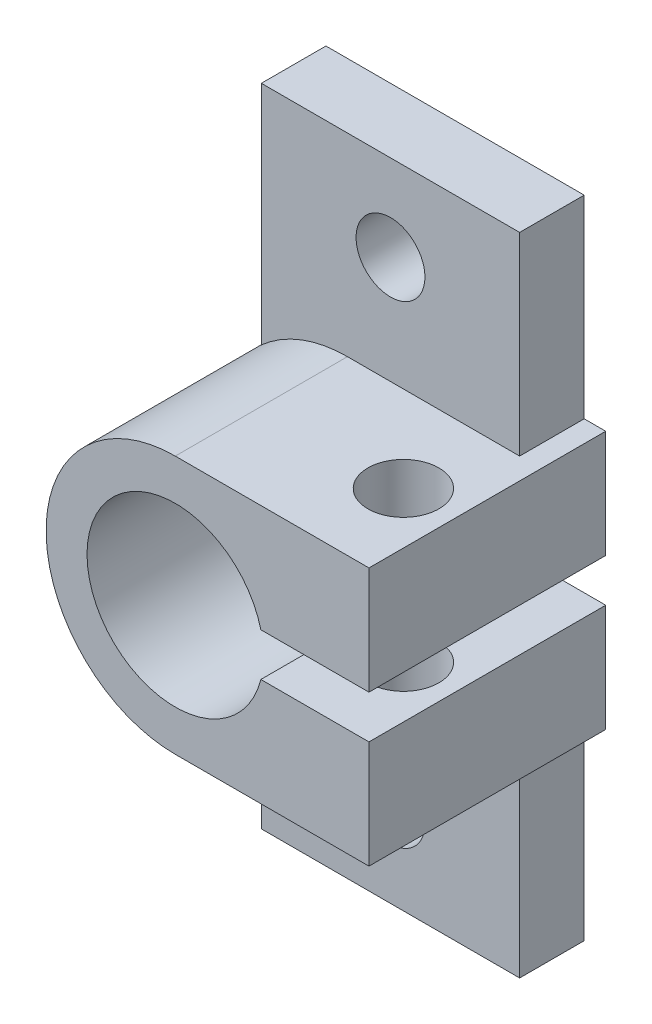
SolidWorks part; units mm, degrees
ref_plane "Plano frontal" through (0, 0, 0) normal (0, 0, 1) x (1, 0, 0)
ref_plane "Plano superior" through (0, 0, 0) normal (0, 1, 0) x (1, 0, 0)
ref_plane "Plano direito" through (0, 0, 0) normal (1, 0, 0) x (0, 0, -1)
sketch "Esboço1" plane through (0, 0, 0) normal (0, 0, 1) x (1, 0, 0)
  line L0 (-4, 15) -> (-4, 0.9)
  line L1 (8, -15) -> (8, -1)
  line L2 (0, 0) -> (8, 0) construction
  line L3 (3.9762, -1) -> (8, -1)
  line L4 (3.9762, 1) -> (8, 1)
  line L5 (0, 1) -> (8, 1) construction
  line L6 (0, -1) -> (8, -1) construction
  line L7 (8, 1) -> (8, 15)
  line L8 (-4, 15) -> (8, 15)
  line L9 (8, -15) -> (-4, -15)
  line L10 (-4, -0.9) -> (-4, -15)
  arc A0 (3.9762, 1) -> (-4, 0.9) centre (0, 0) ccw
  circle A1 centre (2, 11) radius 1.6
  circle A2 centre (2, -11) radius 1.6
  arc A3 (-4, -0.9) -> (3.9762, -1) centre (0, 0) ccw
  point P1 (0, 0)
  point P7 (2, 15)
  point P21 (0, 0)
  dimension "D1" = 12
  dimension "D2" = 3.2
  dimension "D3" = 8.2
  dimension "D4" = 30
  dimension "D7" = 22
  dimension "D8" = 4
  dimension "D5" = 1
  dimension "D6" = 1
extrude "Ressalto-extrusão1" add sketch "Esboço1" along normal blind 3 contours A3 L10 L9 L1 L3 A2 | A0 L4 L7 L8 L0 A1 region at (2.2581, 8.5665, 0) region at (2.2581, -8.5665, 0)
sketch "Esboço2" plane through (0, 0, 3) normal (0, 0, 1) x (1, 0, 0)
  line L0 (9, 6) -> (9, 1)
  line L2 (9, 6) -> (0, 6)
  line L3 (9, -1) -> (9, -6)
  line L10 (9, -6) -> (0, -6)
  line L11 (0, 0) -> (11.2942, 0) construction
  line L12 (9, -1) -> (3.9762, -1)
  line L13 (3.9762, 1) -> (9, 1)
  arc A0 (0, -6) -> (0, 6) centre (0, 0) cw
  arc A1 (3.9762, 1) -> (-4, 0.9) centre (0, 0) ccw construction
  arc A8 (3.9762, 1) -> (3.9762, -1) centre (0, 0) ccw
  point P1 (8.66, 5.869)
  point P7 (8.5, 2.624)
  dimension "D2" = 6
  dimension "D3" = 9
  dimension "D4" = 2
extrude "Ressalto-extrusão2" add sketch "Esboço2" along normal blind 8 and the other way through all
sketch "Esboço3" plane through (0, 6, 0) normal (0, -1, 0) x (1, 0, 0)
  line L0 (4.2, 11) -> (4.2, 3) construction
  line L2 (-6, 3) -> (9, 3) construction
  line L3 (9, 0) -> (9, 11) construction
  line L5 (-6, 11) -> (-6, 0) construction
  line L6 (-4, 3) -> (8, 3) construction
  line L7 (9, 11) -> (0, 11) construction
  line L8 (9, 0) -> (9, 11) construction
  circle A0 centre (6.6, 7) radius 1.65
  point P4 (0, 0)
  point P5 (-6, 3.065)
  point P13 (4.2, 7)
  point P15 (5.4583, 6.6679)
  point P16 (3.9762, 11)
  point P20 (5.901, 7)
  dimension "D1" = 3.3
  dimension "D2" = 2.4
  dimension "D3" = 2.4
extrude "Corte-extrusão1" cut sketch "Esboço3" against normal through all both and the other way through all
